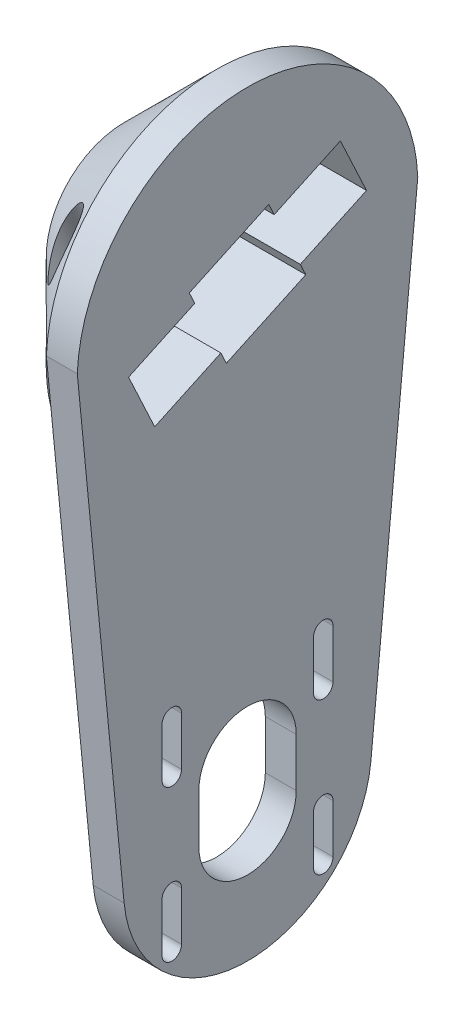
SolidWorks part; units mm, degrees
ref_plane "Front Plane" through (0, 0, 0) normal (0, 0, 1) x (1, 0, 0)
ref_plane "Top Plane" through (0, 0, 0) normal (0, 1, 0) x (1, 0, 0)
ref_plane "Right Plane" through (0, 0, 0) normal (1, 0, 0) x (0, 0, -1)
sketch "Sketch1" plane through (0, 0, 0) normal (1, 0, 0) x (0, 0, -1)
  line L0 (4.3532, 11.9603) -> (-11.9603, 4.3532)
  line L1 (4.3532, 11.9603) -> (11.9603, -4.3532)
  line L2 (-11.9603, 4.3532) -> (-4.3532, -11.9603)
  line L3 (11.9603, -4.3532) -> (-4.3532, -11.9603)
  line L4 (4.3532, 11.9603) -> (-4.3532, -11.9603) construction
  line L5 (-11.9603, 4.3532) -> (11.9603, -4.3532) construction
  line L6 (0, 0) -> (0, -85) construction
  line L7 (-34.9685, 1.4854) -> (-25.35, -97.4642)
  line L8 (25.35, -97.4642) -> (34.9685, 1.4854)
  line L9 (0, -85) -> (0, -103.9417) construction
  arc A0 (34.9685, 1.4854) -> (-34.9685, 1.4854) centre (0, 0) ccw
  arc A1 (-25.35, -97.4642) -> (25.35, -97.4642) centre (0, -95) ccw
  point P12 (0, -120.4695)
  dimension "D1" = 10
  dimension "D2" = 70
  dimension "D6" = 95
  dimension "D7" = 25.35
  dimension "D8" = 25.35
  dimension "D3" = 18
  dimension "D4" = 18
  dimension "D5" = 25
extrude "Boss-Extrude1" add sketch "Sketch1" along normal blind 6.35 contours L7 A0 L1 L3 L2 L0 region at (0, -40.4357, 0)
sketch "Sketch17" plane through (0, 0, 0) normal (-1, 0, 0) x (0, 0, 1)
  line L2 (-34.9685, 1.4854) -> (-25.35, -97.4642)
  line L3 (25.35, -97.4642) -> (34.9685, 1.4854)
  line L4 (-34.9685, 1.4854) -> (-25.35, -97.4642)
  line L6 (25.35, -97.4642) -> (34.9685, 1.4854)
  arc A2 (-25.35, -97.4642) -> (25.35, -97.4642) centre (0, -95) ccw
  arc A3 (-25.35, -97.4642) -> (25.35, -97.4642) centre (0, -95) ccw
  arc A4 (34.9685, 1.4854) -> (-34.9685, 1.4854) centre (0, 0) ccw
  arc A8 (34.9685, 1.4854) -> (-34.9685, 1.4854) centre (0, 0) ccw
  dimension "D1" = 0
sketch "Sketch20" plane through (6.35, 0, 0) normal (1, 0, 0) x (0, 0, -1)
  circle A0 centre (0, 0) radius 35
extrude "Boss-Extrude5" add sketch "Sketch20" along normal blind 19.05
sketch "Sketch21" plane through (0, 0, 0) normal (-1, 0, 0) x (0, 0, 1)
  line L0 (-24.435, 4.3878) -> (-10.8404, -1.9515)
  line L1 (11.9603, 4.3532) -> (4.3532, -11.9603) construction
  line L3 (-4.3532, 11.9603) -> (-11.9603, -4.3532) construction
  line L4 (-4.3532, 11.9603) -> (11.9603, 4.3532) construction
  line L5 (11.9603, 4.3532) -> (10.8404, 1.9515)
  line L7 (-4.3532, 11.9603) -> (-5.4731, 9.5586)
  line L8 (-4.3532, 11.9603) -> (11.9603, 4.3532)
  line L9 (-21.7514, 10.1428) -> (-25.3766, 11.8333) construction
  line L10 (19.0678, -15.8979) -> (5.4731, -9.5586)
  line L11 (19.0678, -15.8979) -> (24.435, -4.3878)
  line L12 (-24.435, 4.3878) -> (-19.0678, 15.8979)
  line L13 (24.435, -4.3878) -> (10.8404, 1.9515)
  line L16 (4.3532, -11.9603) -> (5.4731, -9.5586)
  line L17 (-11.9603, -4.3532) -> (-10.8404, -1.9515)
  line L18 (11.9603, 4.3532) -> (-4.3532, 11.9603)
  line L21 (-10.8404, -1.9515) -> (-11.9603, -4.3532)
  line L24 (-10.8404, -1.9515) -> (-24.435, 4.3878)
  line L27 (-5.4731, 9.5586) -> (-4.3532, 11.9603)
  line L29 (-5.4731, 9.5586) -> (-19.0678, 15.8979)
  line L30 (5.4731, -9.5586) -> (4.3532, -11.9603)
  line L31 (10.8404, 1.9515) -> (11.9603, 4.3532)
  line M13 (-11.9603, -4.3532) -> (-4.3532, 11.9603)
  line M14 (-4.3532, 11.9603) -> (11.9603, 4.3532)
  line M15 (11.9603, 4.3532) -> (4.3532, -11.9603)
  line M16 (4.3532, -11.9603) -> (-11.9603, -4.3532)
  dimension "D1" = 15
  dimension "D2" = 12.7
extrude "Cut-Extrude14" cut sketch "Sketch21" against normal through all contours L29 L12 L0 M13 | M13 M16 M15 M14 | L11 L13 L10 M15 region at (0, 6.9732, -14.9541) region at (0, 0, 0) region at (0, -6.9732, 14.9541)
chamfer "Chamfer1" distance 19.05 angle 45 1 edges at (25.4, 0, -35)
sketch "Sketch22" plane through (0, 5.7551, 2.6836) normal (0, -0.9063, -0.4226) x (-1, 0, 0)
  line L0 (-25.4, -9) -> (0, -9) construction
  line L1 (-25.4, -9) -> (-25.4, -14.6315) construction
  circle A0 centre (-13.4, -16.5) radius 3.175
  dimension "D2" = 12
  dimension "D3" = 6.35
  dimension "D1" = 7.5
extrude "Cut-Extrude15" cut sketch "Sketch22" against normal through all
ref_plane "Plane1" through (0, 10.2866, 4.7967) normal (0, -0.9063, -0.4226) x (-1, 0, 0)
sketch "Sketch24" plane through (0, 10.2866, 4.7967) normal (0, -0.9063, -0.4226) x (-1, 0, 0)
  circle A0 centre (-13.4, -16.5) radius 5
  dimension "D1" = 10
extrude "Cut-Extrude16" cut sketch "Sketch24" against normal through all
sketch "Sketch25" plane through (0, -5.7551, -2.6836) normal (0, 0.9063, 0.4226) x (1, 0, 0)
  circle A0 centre (13.4, -16.5) radius 3.175 construction
  circle A1 centre (13.4, -16.5) radius 3.175
  circle A2 centre (13.4, -16.5) radius 2.3813
  dimension "D1" = 0.7937
extrude "Cut-Extrude17" cut sketch "Sketch25" against normal blind 10 contours A2 region at (13.4, -12.7283, 12.2705)
ref_plane "Plane2" through (0, 0, 0) normal (0, 0.4226, -0.9063) x (-1, 0, 0)
mirror "Mirror1" about plane through (0, 0, 0) normal (0, 0.4226, -0.9063) of "Cut-Extrude15", "Cut-Extrude17", "Cut-Extrude16"
sketch "Sketch19" plane through (6.35, 0, 0) normal (1, 0, 0) x (0, 0, -1)
  line L0 (0, -95.14) -> (0, -85.14)
  line L1 (0, -85.14) -> (15.5563, -69.5837) construction
  line L2 (15.5563, -79.5837) -> (15.5563, -69.5837) construction
  line L3 (13.5563, -79.5837) -> (13.5563, -69.5837)
  line L4 (17.5563, -79.5837) -> (17.5563, -69.5837)
  line L5 (-10, -95.14) -> (-10, -85.14)
  line L6 (10, -95.14) -> (10, -85.14)
  line L7 (0, -90.14) -> (7.4061, -90.14) construction
  line L8 (15.5563, -79.5837) -> (0, -95.14) construction
  line L9 (17.5563, -100.6963) -> (17.5563, -110.6963)
  line L10 (13.5563, -100.6963) -> (13.5563, -110.6963)
  line L11 (-17.5563, -79.5837) -> (-17.5563, -69.5837)
  line L12 (-13.5563, -79.5837) -> (-13.5563, -69.5837)
  line L13 (-13.5563, -100.6963) -> (-13.5563, -110.6963)
  line L14 (-17.5563, -100.6963) -> (-17.5563, -110.6963)
  line L15 (-15.5563, -79.5837) -> (0, -95.14) construction
  line L16 (0, -95.14) -> (-15.5563, -110.6963) construction
  line L17 (0, -95.14) -> (15.5563, -110.6963) construction
  arc A2 (-10, -95.14) -> (10, -95.14) centre (0, -95.14) ccw
  arc A3 (17.5563, -110.6963) -> (13.5563, -110.6963) centre (15.5563, -110.6963) cw
  arc A4 (13.5563, -100.6963) -> (17.5563, -100.6963) centre (15.5563, -100.6963) cw
  arc A6 (17.5563, -69.5837) -> (13.5563, -69.5837) centre (15.5563, -69.5837) ccw
  arc A7 (13.5563, -79.5837) -> (17.5563, -79.5837) centre (15.5563, -79.5837) ccw
  arc A8 (-17.5563, -69.5837) -> (-13.5563, -69.5837) centre (-15.5563, -69.5837) cw
  arc A9 (10, -85.14) -> (-10, -85.14) centre (0, -85.14) ccw
  arc A10 (-13.5563, -79.5837) -> (-17.5563, -79.5837) centre (-15.5563, -79.5837) cw
  arc A11 (-13.5563, -100.6963) -> (-17.5563, -100.6963) centre (-15.5563, -100.6963) ccw
  arc A13 (-17.5563, -110.6963) -> (-13.5563, -110.6963) centre (-15.5563, -110.6963) ccw
  point P8 (0, -90.14)
  dimension "D3" = 22
  dimension "D5" = 4
  dimension "D6" = 10
  dimension "D4" = 4
  dimension "D2" = 10
  dimension "D7" = 45
extrude "Cut-Extrude18" cut sketch "Sketch19" against normal blind 10 contours L6 A9 L5 A2 | A10 L12 A8 L11 | L14 A13 L13 A11 | A4 L10 A3 L9 | L4 A6 L3 A7 region at (6.35, -90.14, 9.6394) region at (6.35, -105.6963, -15.5563) region at (6.35, -74.5837, 15.5563) region at (6.35, -105.6963, 15.5563)
mirror "Mirror2" about plane through (0, 0, 0) normal (1, 0, 0) of bodies 126
delete or keep bodies "Body-Delete/Keep 1" type delete bodies bodies 126
equation "\".75i\"=14.27"
